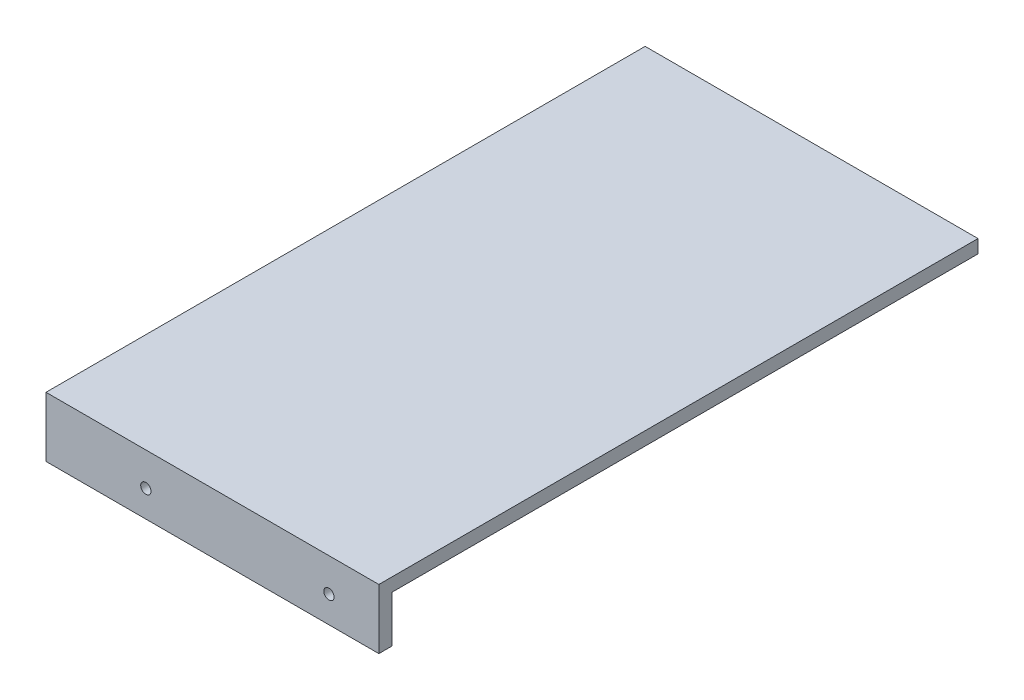
SolidWorks part; units mm, degrees
ref_plane "Front Plane" through (0, 0, 0) normal (0, 0, 1) x (1, 0, 0)
ref_plane "Top Plane" through (0, 0, 0) normal (0, 1, 0) x (1, 0, 0)
ref_plane "Right Plane" through (0, 0, 0) normal (1, 0, 0) x (0, 0, -1)
sketch "Sketch1" plane through (-1647.1695, 0, 0) normal (1, 0, 0) x (0, 0, -1)
  line L0 (-1369.8257, 767.8493) -> (-1369.8257, 763.1367) construction
  line L1 (-1369.8257, 769.8493) -> (-1189.8257, 769.8493)
  line L2 (-1369.8257, 769.8493) -> (-1369.8257, 751.8493)
  line L3 (-1369.8257, 751.8493) -> (-1189.8257, 751.8493)
  line L4 (-1189.8257, 769.8493) -> (-1189.8257, 751.8493)
  line L5 (-1369.8257, 769.8493) -> (-789.8257, 769.8493) construction
  line L6 (-1369.8257, 751.8493) -> (-789.8257, 751.8493) construction
  line L7 (-1339.8257, 756.5619) -> (-1339.8257, 763.1367) construction
  line L8 (-1369.8257, 756.5619) -> (-789.8257, 756.5619) construction
  line L9 (-1369.8257, 763.1367) -> (-789.8257, 763.1367) construction
  line L10 (-1339.8257, 759.8493) -> (-1219.8257, 759.8493) construction
  circle A0 centre (-1219.8257, 759.8493) radius 1.55
  circle A1 centre (-1339.8257, 759.8493) radius 1.55
  dimension "D4" = 3.1
  dimension "D5" = 3.1
  dimension "D1" = 180
  dimension "D2" = 30
  dimension "D3" = 30
extrude "Boss-Extrude1" add sketch "Sketch1" along normal blind 4
sketch "Sketch2" plane through (0, 0, 1369.8257) normal (0, 0, -1) x (-1, 0, 0)
  line L0 (1647.1695, 751.8493) -> (967.1695, 751.8493) construction
  line L1 (1647.1695, 769.8493) -> (1547.1695, 769.8493)
  line L2 (1647.1695, 769.8493) -> (1647.1695, 751.8493)
  line L3 (1647.1695, 751.8493) -> (1547.1695, 751.8493)
  line L4 (1547.1695, 769.8493) -> (1547.1695, 751.8493)
  line L5 (1617.1695, 763.1367) -> (1617.1695, 756.5619) construction
  line L6 (1647.1695, 763.1367) -> (967.1695, 763.1367) construction
  line L7 (1647.1695, 756.5619) -> (967.1695, 756.5619) construction
  line L8 (1617.1695, 759.8493) -> (1562.1695, 759.8493) construction
  circle A0 centre (1617.1695, 759.8493) radius 1.55
  circle A1 centre (1562.1695, 759.8493) radius 1.55
  dimension "D4" = 3.1
  dimension "D5" = 3.1
  dimension "D1" = 100
  dimension "D2" = 30
  dimension "D3" = 15
extrude "Boss-Extrude2" add sketch "Sketch2" along normal blind 4
sketch "Sketch3" plane through (0, 0, 1365.8257) normal (0, 0, -1) x (-1, 0, 0)
  line L0 (1643.1695, 751.8493) -> (1643.1695, 769.8493) construction
  line L1 (1547.1695, 769.8493) -> (1643.1695, 769.8493)
  line L2 (1547.1695, 769.8493) -> (1547.1695, 765.8493)
  line L3 (1547.1695, 765.8493) -> (1643.1695, 765.8493)
  line L4 (1643.1695, 769.8493) -> (1643.1695, 765.8493)
  dimension "D1" = 4
extrude "Boss-Extrude3" add sketch "Sketch3" along normal up to surface (176 mm away) up to face at (-1645.1695, 760.8493, 1189.8257)
